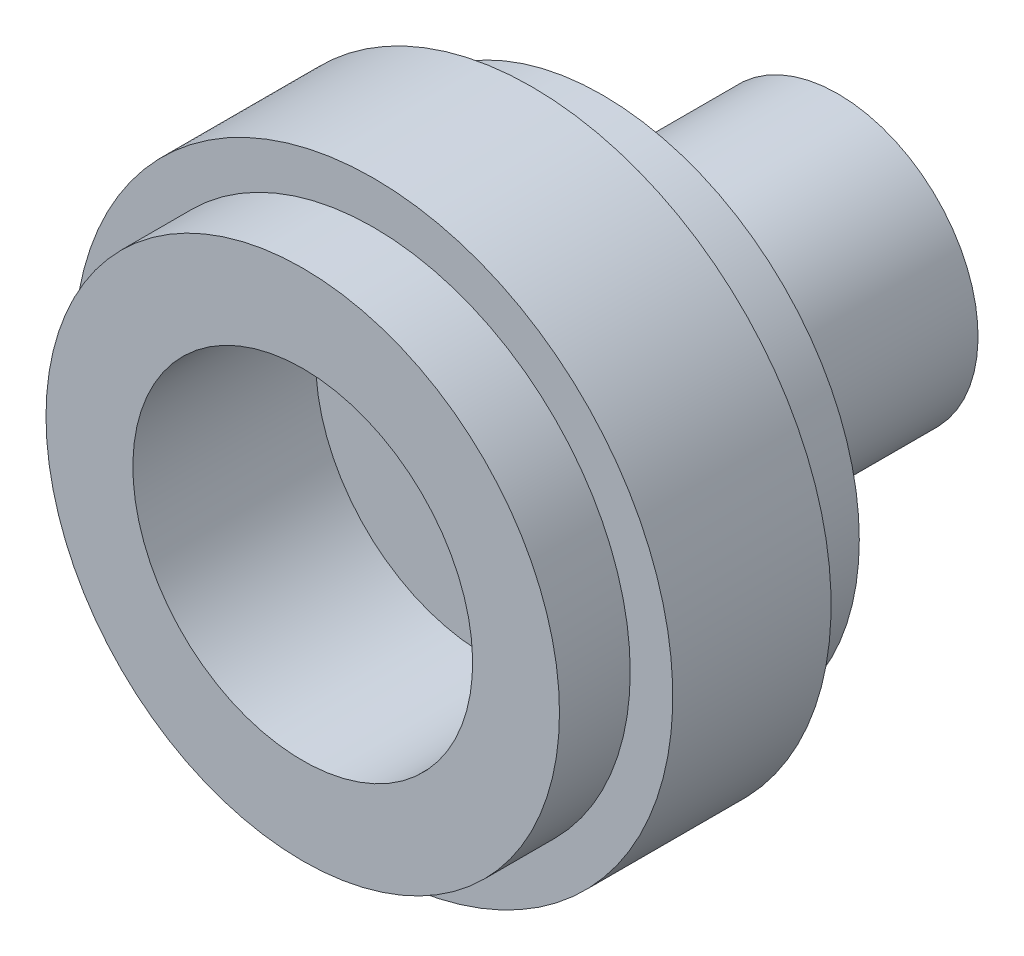
SolidWorks part; units mm, degrees
material "Custom Plastic"
ref_plane "Front Plane" through (0, 0, 0) normal (0, 0, 1) x (1, 0, 0)
ref_plane "Top Plane" through (0, 0, 0) normal (0, 1, 0) x (1, 0, 0)
ref_plane "Right Plane" through (0, 0, 0) normal (1, 0, 0) x (0, 0, -1)
sketch "Sketch2" plane through (0, 0, 0) normal (1, 0, 0) x (0, 0, -1)
  line L0 (0, 0) -> (-6.9967, 0) construction
  line L1 (0, 0) -> (0, 9.8665) construction
  line L2 (-5.4356, 6.1595) -> (1.1938, 6.1595)
  line L3 (1.1938, 6.1595) -> (1.1938, 1.7526)
  line L4 (1.1938, 1.7526) -> (13.97, 1.7526)
  line L5 (13.97, 1.7526) -> (13.97, 5.08)
  line L6 (13.97, 5.08) -> (5.4356, 5.08)
  line L7 (5.4356, 5.08) -> (5.4356, 9.3091)
  line L8 (5.4356, 9.3091) -> (2.8702, 9.3091)
  line L9 (2.8702, 9.3091) -> (2.8702, 10.8521)
  line L10 (2.8702, 10.8521) -> (-2.8702, 10.8521)
  line L11 (-2.8702, 10.8521) -> (-2.8702, 9.3091)
  line L12 (-2.8702, 9.3091) -> (-5.4356, 9.3091)
  line L13 (-5.4356, 9.3091) -> (-5.4356, 6.1595)
  dimension "D1" = 12.319
  dimension "D2" = 3.5052
  dimension "D3" = 6.6294
  dimension "D4" = 18.6182
  dimension "D5" = 5.7404
  dimension "D6" = 10.8712
  dimension "D7" = 21.7043
  dimension "D8" = 10.16
  dimension "D9" = 19.4056
revolve "Revolve1" add sketch "Sketch2" angle 360 about L0
